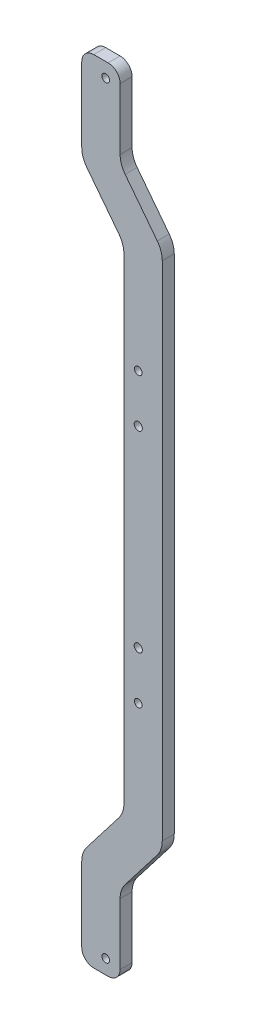
SolidWorks part; units mm, degrees
material "Thornel Mat VMA"
ref_plane "前视基准面" through (0, 0, 0) normal (0, 0, 1) x (1, 0, 0)
ref_plane "上视基准面" through (0, 0, 0) normal (0, 1, 0) x (1, 0, 0)
ref_plane "右视基准面" through (0, 0, 0) normal (1, 0, 0) x (0, 0, -1)
sketch "草图2" plane through (0, 0, 0) normal (0, 0, 1) x (1, 0, 0)
  line L8 (-16, -33.6265) -> (-16, 36.3735)
  line L10 (-16, 1.3735) -> (-30.213, 1.3735) construction
  line L12 (-16, -33.6265) -> (-16, -97.9019)
  line L16 (-18.083, -104.011) -> (-31.4817, -121.3748)
  line L17 (-33.5647, -127.4839) -> (-33.5647, -158.5184)
  line L18 (-28.5647, -163.5184) -> (-22.5647, -163.5184)
  line L20 (-17.5647, -158.5184) -> (-17.5647, -132.9394)
  line L21 (-15.4817, -126.8303) -> (-2.083, -109.4664)
  line L22 (0, -103.3573) -> (0, 4.2244)
  line L23 (0, 106.1043) -> (0, -1.4775)
  line L24 (-15.4817, 129.5772) -> (-2.083, 112.2134)
  line L25 (-17.5647, 161.2653) -> (-17.5647, 135.6863)
  line L26 (-28.5647, 166.2653) -> (-22.5647, 166.2653)
  line L27 (-33.5647, 130.2308) -> (-33.5647, 161.2653)
  line L28 (-18.083, 106.7579) -> (-31.4817, 124.1217)
  line L29 (-16, 36.3735) -> (-16, 100.6488)
  circle A0 centre (-23.5647, -157.5184) radius 1.6
  arc A1 (-16, -97.9019) -> (-18.083, -104.011) centre (-26, -97.9019) cw
  arc A2 (-17.5647, -132.9394) -> (-15.4817, -126.8303) centre (-7.5647, -132.9394) cw
  arc A3 (-2.083, -109.4664) -> (0, -103.3573) centre (-10, -103.3573) ccw
  arc A4 (-31.4817, -121.3748) -> (-33.5647, -127.4839) centre (-23.5647, -127.4839) ccw
  arc A5 (-22.5647, -163.5184) -> (-17.5647, -158.5184) centre (-22.5647, -158.5184) ccw
  arc A6 (-33.5647, -158.5184) -> (-28.5647, -163.5184) centre (-28.5647, -158.5184) ccw
  circle A7 centre (-10.0011, -58.6265) radius 1.6
  circle A8 centre (-10.0011, -38.6265) radius 1.7015
  circle A9 centre (-10.0011, 41.3735) radius 1.7015
  circle A10 centre (-10.0011, 61.3735) radius 1.6
  arc A11 (-33.5647, 161.2653) -> (-28.5647, 166.2653) centre (-28.5647, 161.2653) cw
  arc A12 (-22.5647, 166.2653) -> (-17.5647, 161.2653) centre (-22.5647, 161.2653) cw
  arc A13 (-31.4817, 124.1217) -> (-33.5647, 130.2308) centre (-23.5647, 130.2308) cw
  arc A14 (-2.083, 112.2134) -> (0, 106.1043) centre (-10, 106.1043) cw
  arc A15 (-17.5647, 135.6863) -> (-15.4817, 129.5772) centre (-7.5647, 135.6863) ccw
  arc A16 (-16, 100.6488) -> (-18.083, 106.7579) centre (-26, 100.6488) ccw
  circle A17 centre (-23.5647, 160.2653) radius 1.6
  point P13 (-25.5647, -163.5184)
  line M5 (0, -63.1089) -> (0, -43.1089)
  line M6 (0, -43.1089) -> (-18, -43.1089)
  line M8 (-18, -63.1089) -> (0, -63.1089)
  dimension "D1" = 3.2
  dimension "D2" = 6
  dimension "D3" = 6
  dimension "D4" = 16
  dimension "D5" = 16
  dimension "D8" = 5
  dimension "D6" = 16
  dimension "D7" = 10
extrude "凸台-拉伸1" add sketch "草图2" along normal blind 5 contours L17 A6 L18 A5 L20 A2 L21 A3 L22 L12 A1 L16 A4 A0 M8 | L12 A7 M6 M8 M5 | A16 L29 L8 L12 L22 L23 A14 L24 A15 L25 A12 L26 A11 L27 A13 L28 A10 A8 A9 A17 M6 region at (-12.1145, 62.935, 0) region at (-7.9484, -52.9666, 0) region at (-16.3423, -112.9095, 0)
